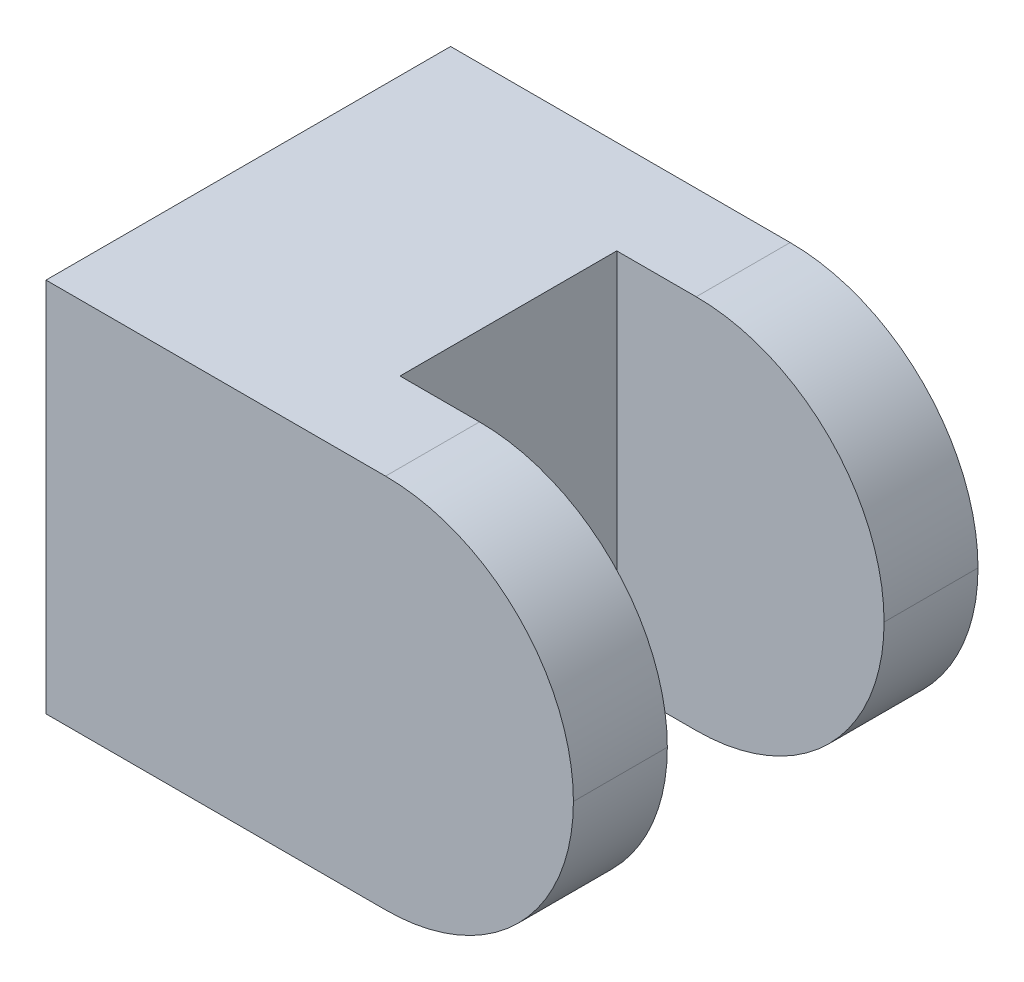
SolidWorks part; units mm, degrees
ref_plane "Ön Düzlem" through (0, 0, 0) normal (0, 0, 1) x (1, 0, 0)
ref_plane "Üst Düzlem" through (0, 0, 0) normal (0, 1, 0) x (1, 0, 0)
ref_plane "Sağ Düzlem" through (0, 0, 0) normal (1, 0, 0) x (0, 0, -1)
sketch "Çizim1" plane through (0, 0, 0) normal (0, 0, 1) x (1, 0, 0)
  line L1 (0, 0) -> (73, 0)
  line L2 (0, 0) -> (0, 52)
  line L3 (0, 52) -> (73, 52)
  line L4 (73, 0) -> (73, 52)
  dimension "D1" = 52
  dimension "D2" = 73
extrude "Yükseklik-Ekstrüzyon1" add sketch "Çizim1" along normal blind 56
sketch "Çizim2" plane through (0, 52, 0) normal (0, 1, 0) x (1, 0, 0)
  line L0 (73, -56) -> (73, 0) construction
  line L1 (73, -13) -> (36, -13)
  line L2 (73, -13) -> (73, -43)
  line L3 (73, -43) -> (36, -43)
  line L4 (36, -13) -> (36, -43)
  line L8 (73, -56) -> (0, -56) construction
  dimension "D1" = 30
  dimension "D2" = 13
  dimension "D3" = 37
extrude "Kes-Ekstrüzyon1" cut sketch "Çizim2" against normal through all
fillet "Radyus1" radius 26 1 edges at (73, 52, 49.5)
fillet "Radyus2" radius 26 1 edges at (73, 0, 49.5)
fillet "Radyus3" radius 26 1 edges at (73, 52, 6.5)
fillet "Radyus5" radius 26 1 edges at (73, 0, 6.5)
